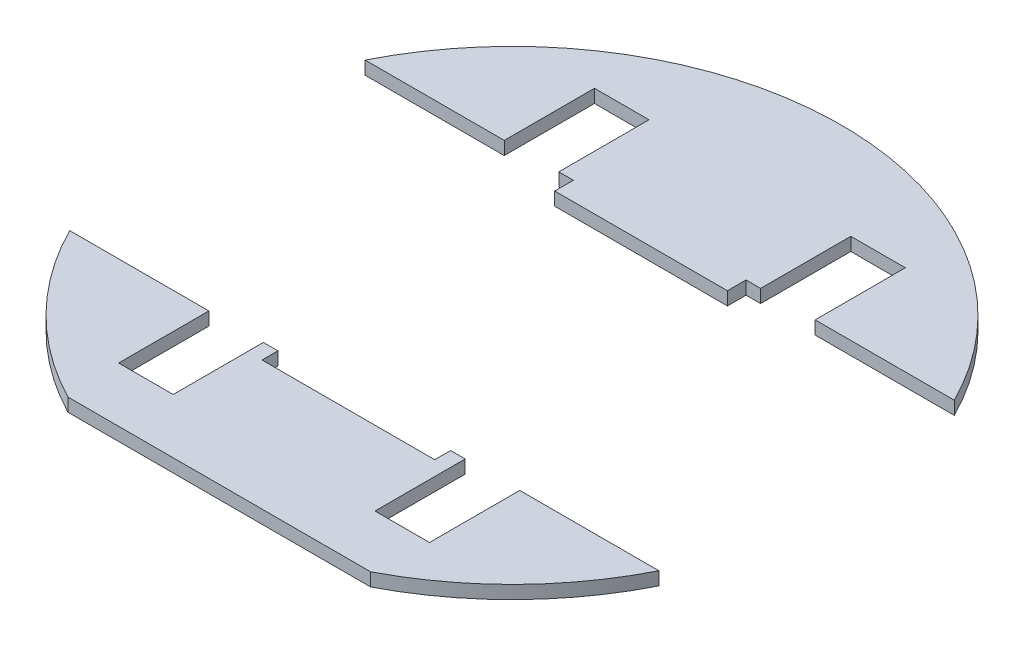
SolidWorks part; units mm, degrees
ref_plane "Front Plane" through (0, 0, 0) normal (0, 0, 1) x (1, 0, 0)
ref_plane "Top Plane" through (0, 0, 0) normal (0, 1, 0) x (1, 0, 0)
ref_plane "Right Plane" through (0, 0, 0) normal (1, 0, 0) x (0, 0, -1)
sketch "Sketch1" plane through (0, 0, 0) normal (0, 1, 0) x (1, 0, 0)
  line L0 (-33.2911, -64.4046) -> (33.2911, -64.4046)
  line L1 (0, -83.2398) -> (0, 0) construction
  line L2 (0, -83.2398) -> (33.2911, -64.4046) construction
  arc A0 (33.2911, -64.4046) -> (-33.2911, -64.4046) centre (0, 0) ccw
  circle A1 centre (0, -83.2398) radius 38.25 construction
  dimension "D1" = 145
  dimension "D2" = 76.5
  dimension "D3" = 60.5
extrude "Boss-Extrude1" add sketch "Sketch1" along normal blind 2.9
sketch "Sketch2" plane through (0, 2.9, 0) normal (0, 1, 0) x (1, 0, 0)
  line L0 (18, -36) -> (-18, -36) construction
  line L1 (-34.2, -52.3449) -> (-22.2, -52.3449)
  line L2 (-34.2, -52.3449) -> (-34.2, 52.3449)
  line L3 (-34.2, 52.3449) -> (-22.2, 52.3449)
  line L4 (-22.2, -52.3449) -> (-22.2, -32.5)
  line L5 (-19, -32.5) -> (-22.2, -32.5) construction
  line L6 (-22.2, -52.3449) -> (-22.2, -32.5)
  line L7 (-19, -32.5) -> (-22.2, -32.5)
  line L8 (19, 28.4) -> (-19, 28.4) construction
  line L9 (18, -36) -> (-18, -36)
  line L10 (-19, 32.5) -> (-22.2, 32.5) construction
  line L11 (-19, 32.5) -> (-22.2, 32.5)
  line L12 (19, 28.4) -> (-19, 28.4)
  line L13 (-19, -32.5) -> (-19, -36)
  line L14 (-19, -36) -> (-18, -36)
  line L15 (-19, 32.5) -> (-19, 28.4)
  line L16 (-22.2, 32.5) -> (-22.2, 52.3449)
  line L17 (0, 0) -> (0, -64.4046) construction
  line L18 (-33.2911, -64.4046) -> (33.2911, -64.4046) construction
  line L19 (22.2, 32.5) -> (22.2, 52.3449)
  line L20 (19, 32.5) -> (19, 28.4)
  line L21 (19, -36) -> (18, -36)
  line L22 (19, -32.5) -> (19, -36)
  line L23 (19, 32.5) -> (22.2, 32.5)
  line L24 (19, -32.5) -> (22.2, -32.5)
  line L25 (22.2, -52.3449) -> (22.2, -32.5)
  line L26 (22.2, -52.3449) -> (22.2, -32.5)
  line L27 (34.2, 52.3449) -> (22.2, 52.3449)
  line L28 (34.2, -52.3449) -> (34.2, 52.3449)
  line L29 (34.2, -52.3449) -> (22.2, -52.3449)
extrude "Cut-Extrude1" cut sketch "Sketch2" against normal through all contours L29 L28 L27 L19 L23 L20 L12 L15 L11 L16 L3 L2 L1 L4 L7 L13 L14 L9 L21 L22 L24 L25 region at (0, 2.9, 1.7299)
sketch "Sketch3" plane through (0, 2.9, 0) normal (0, 1, 0) x (1, 0, 0)
  line L0 (-34.2, 32.5) -> (-34.2, -32.5)
  line L1 (-72.5, -32.5) -> (-34.2, -32.5)
  line L2 (-72.5, -32.5) -> (-72.5, 32.5)
  line L3 (-72.5, 32.5) -> (-34.2, 32.5)
  line L4 (72.5, -32.5) -> (72.5, 32.5)
  line L5 (-72.5, -32.5) -> (72.5, 32.5) construction
  line L6 (-72.5, 32.5) -> (72.5, -32.5) construction
  line L7 (-34.2, -52.3449) -> (-34.2, 52.3449) construction
  line L8 (34.2, 32.5) -> (34.2, -32.5)
  line L9 (34.2, -52.3449) -> (34.2, 52.3449) construction
  line L10 (34.2, 32.5) -> (72.5, 32.5)
  line L11 (34.2, -32.5) -> (72.5, -32.5)
  arc A0 (33.2911, -64.4046) -> (-33.2911, -64.4046) centre (0, 0) ccw construction
  point P0 (0, 0)
  dimension "D1" = 65
extrude "Cut-Extrude2" cut sketch "Sketch3" against normal through all
equation "\"smallPulleyTeeth\"= 15"
equation "\"largePulleyTeeth\"= 30"
equation "\"eighthThick\"= 2.9mm"
equation "\"sixteenthThick\"= 1.7mm"
equation "\"quarterThick\"=6.0mm"
equation "\"OD\"= 145mm"
equation "\"puckAngle\"= 60.5deg"
equation "\"puckDiam\"= 76.5mm"
equation "\"axlePress\"= 5.9mm"
equation "\"press\"= 0.2mm"
equation "\"wheelClear\"= 0.3mm"
equation "\"10-32clear\"= 4.8mm"
equation "\"6-32clear\"= 3.3mm"
equation "\"8-32clear\"= 4.0mm"
equation "\"4-40clear\"= 3.0mm"
equation "\"wheelHeight\"= 22mm"
equation "\"wheelWell\"= 65mm"
equation "\"D1@Sketch1\"=\"OD\""
equation "\"D1@Boss-Extrude1\"=\"eighthThick\""
equation "\"D2@Sketch1\"=\"puckDiam\""
equation "\"D3@Sketch1\"=\"puckAngle\""
equation "\"D1@Sketch3\"=\"wheelWell\""
